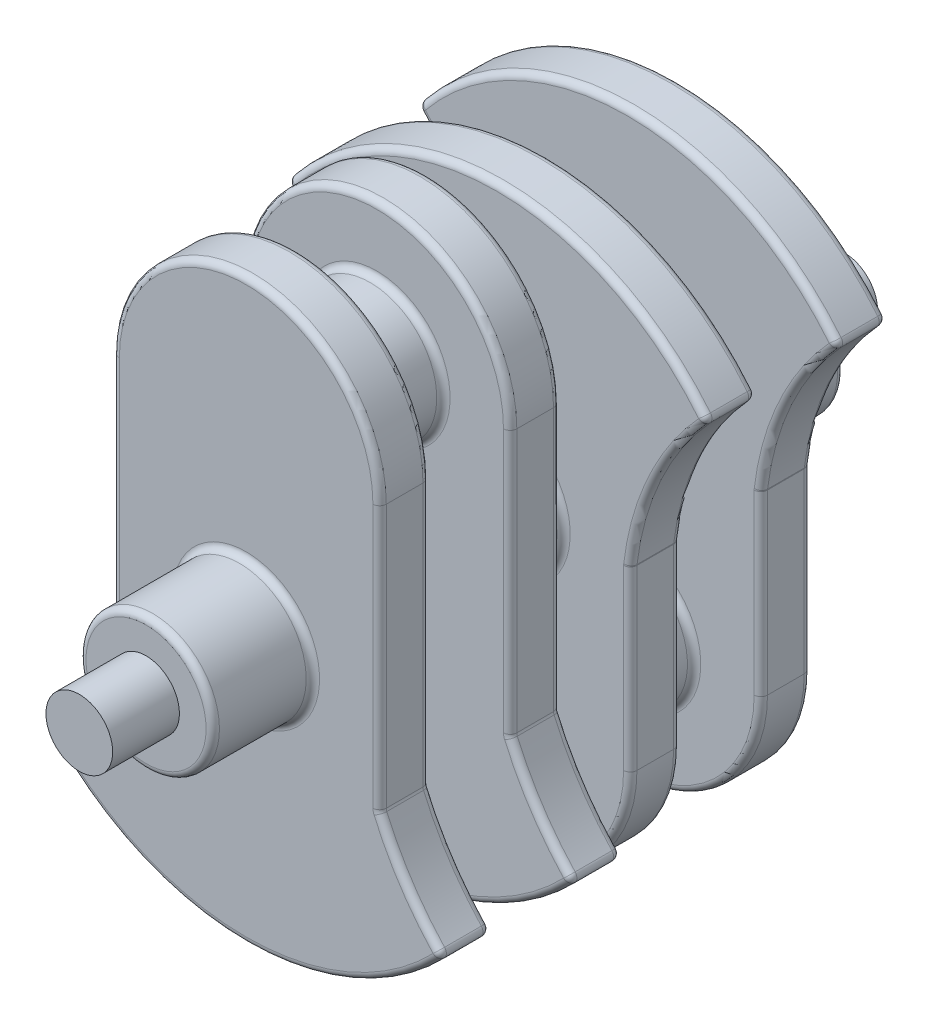
SolidWorks part; units mm, degrees
material "AISI 4340 Steel, normalized"
ref_plane "Front Plane" through (0, 0, 0) normal (0, 0, 1) x (1, 0, 0)
ref_plane "Top Plane" through (0, 0, 0) normal (0, 1, 0) x (1, 0, 0)
ref_plane "Right Plane" through (0, 0, 0) normal (1, 0, 0) x (0, 0, -1)
sketch "Sketch1" plane through (0, 0, 0) normal (0, 0, 1) x (1, 0, 0)
  circle A0 centre (0, 0) radius 20
  dimension "D1" = 20
extrude "Boss-Extrude1" add sketch "Sketch1" along normal blind 30
sketch "Sketch8" plane through (0, 0, 0) normal (0, 0, -1) x (-1, 0, 0)
  line L0 (-40, 53.333) -> (-40, -25.971)
  line L1 (40, 53.333) -> (40, -25.971)
  arc A0 (40, 53.333) -> (-40, 53.333) centre (0, 53.333) ccw
  arc A5 (-58.7669, -54.2813) -> (58.7669, -54.2813) centre (0, 0) ccw
  arc A6 (-40, -25.971) -> (-58.7669, -54.2813) centre (-125, 10) cw
  arc A7 (40, -25.971) -> (58.7669, -54.2813) centre (125, 10) ccw
  dimension "D1" = 40
  dimension "D2" = 80
  dimension "D3" = 53.333
  dimension "D5" = 10
  dimension "D6" = 125
extrude "Boss-Extrude5" add sketch "Sketch8" along normal blind 15
sketch "Sketch2" plane through (0, 0, 30) normal (0, 0, 1) x (1, 0, 0)
  circle A0 centre (0, 0) radius 10
  dimension "D1" = 10
extrude "Boss-Extrude2" add sketch "Sketch2" along normal blind 20
sketch "Sketch9" plane through (0, 0, -15) normal (0, 0, -1) x (-1, 0, 0)
  circle A0 centre (0, 53.333) radius 20
  dimension "D2" = 20
  dimension "D1" = 53.333
extrude "Boss-Extrude6" add sketch "Sketch9" along normal blind 24.13
ref_plane "Plane4" through (0, 0, -75.13) normal (0, 0, -1) x (-1, 0, 0)
sketch "Sketch10" plane through (0, 0, -39.13) normal (0, 0, -1) x (-1, 0, 0)
  line L0 (-40, -53.333) -> (-40, 0)
  line L1 (40, -53.333) -> (40, 0)
  arc A0 (-40, -53.333) -> (40, -53.333) centre (0, -53.333) ccw
  arc A1 (-40, 0) -> (-63.131, 49.1373) centre (-125, -10) ccw
  arc A2 (40, 0) -> (63.131, 49.1373) centre (125, -10) cw
  arc A3 (-63.131, 49.1373) -> (63.131, 49.1373) centre (0, 0) cw
  dimension "D1" = 40
  dimension "D5" = 10
  dimension "D3" = 80
  dimension "D2" = 53.333
  dimension "D4" = 125
extrude "Boss-Extrude7" add sketch "Sketch10" along normal blind 15 from surface starting at plane "Plane4"
ref_plane "Plane3" through (0, 0, -114.26) normal (0, 0, -1) x (-1, 0, 0)
sketch "Sketch12" plane through (0, 0, -114.26) normal (0, 0, -1) x (-1, 0, 0)
  line L2 (40, -53.333) -> (40, 0)
  line L3 (40, -53.333) -> (40, 0)
  line L4 (-40, 0) -> (-40, -53.333)
  line L5 (-40, 0) -> (-40, -53.333)
  arc A12 (-40, -53.333) -> (40, -53.333) centre (0, -53.333) ccw
  arc A13 (63.131, 49.1373) -> (40, 0) centre (125, -10) ccw
  arc A14 (63.131, 49.1373) -> (-63.131, 49.1373) centre (0, 0) ccw
  arc A15 (-40, 0) -> (-63.131, 49.1373) centre (-125, -10) ccw
  arc A16 (-40, -53.333) -> (40, -53.333) centre (0, -53.333) ccw
  arc A17 (63.131, 49.1373) -> (40, 0) centre (125, -10) ccw
  arc A18 (63.131, 49.1373) -> (-63.131, 49.1373) centre (0, 0) ccw
  arc A19 (-40, 0) -> (-63.131, 49.1373) centre (-125, -10) ccw
  dimension "D1" = 0
extrude "Boss-Extrude8" add sketch "Sketch12" along normal blind 15
sketch "Sketch14" plane through (0, 0, -90.13) normal (0, 0, -1) x (-1, 0, 0)
  circle A0 centre (0, -53.333) radius 20
  dimension "D2" = 20
  dimension "D1" = 53.333
extrude "Boss-Extrude9" add sketch "Sketch14" along normal up to next
sketch "Sketch15" plane through (0, 0, -129.26) normal (0, 0, -1) x (-1, 0, 0)
  circle A1 centre (0, 0) radius 20
  circle A2 centre (0, 0) radius 20
  dimension "D1" = 0
extrude "Boss-Extrude10" add sketch "Sketch15" along normal blind 30
sketch "Sketch16" plane through (0, 0, -159.26) normal (0, 0, -1) x (-1, 0, 0)
  circle A1 centre (0, 0) radius 10
  circle A2 centre (0, 0) radius 10
  dimension "D1" = 0
extrude "Boss-Extrude11" add sketch "Sketch16" along normal blind 20
sketch "Sketch18" plane through (0, 0, -39.13) normal (0, 0, -1) x (-1, 0, 0)
  line L2 (-40, 53.333) -> (-40, -25.971)
  line L3 (-40, 53.333) -> (-40, -25.971)
  line L4 (40, -25.971) -> (40, 53.333)
  line L5 (40, -25.971) -> (40, 53.333)
  arc A4 (40, 53.333) -> (-40, 53.333) centre (0, 53.333) ccw
  arc A5 (-58.7669, -54.2813) -> (-40, -25.971) centre (-125, 10) ccw
  arc A6 (-58.7669, -54.2813) -> (58.7669, -54.2813) centre (0, 0) ccw
  arc A7 (40, -25.971) -> (58.7669, -54.2813) centre (125, 10) ccw
  arc A8 (40, 53.333) -> (-40, 53.333) centre (0, 53.333) ccw
  arc A9 (-58.7669, -54.2813) -> (-40, -25.971) centre (-125, 10) ccw
  arc A10 (-58.7669, -54.2813) -> (58.7669, -54.2813) centre (0, 0) ccw
  arc A11 (40, -25.971) -> (58.7669, -54.2813) centre (125, 10) ccw
  dimension "D1" = 0
extrude "Boss-Extrude12" add sketch "Sketch18" along normal blind 15
sketch "Sketch19" plane through (0, 0, -54.13) normal (0, 0, -1) x (-1, 0, 0)
  circle A1 centre (0, 0) radius 20
  circle A2 centre (0, 0) radius 20
  dimension "D1" = 0
extrude "Boss-Extrude13" add sketch "Sketch19" along normal up to next
fillet "Fillet1" radius 2 32 edges at (0, -80, -39.13) (-48.0699, -40.9968, -39.13) (-40, 13.681, -39.13) (40, 13.681, -39.13) (48.0699, -40.9968, -39.13) (0, -80, -54.13) (-48.0699, -40.9968, -54.13) (-40, 13.681, -54.13) (0, 93.333, -54.13) (40, 13.681, -54.13) (48.0699, -40.9968, -54.13) (58.7669, -54.2813, -46.63) (40, -25.971, -46.63) (-40, -25.971, -46.63) (-58.7669, -54.2813, -46.63) (0, 93.333, -39.13) (40, 13.681, 0) (48.0699, -40.9968, 0) (0, -80, 0) (-48.0699, -40.9968, 0) (-40, 13.681, 0) (0, 93.333, -15) (40, 13.681, -15) (48.0699, -40.9968, -15) (0, -80, -15) (-48.0699, -40.9968, -15) (-40, 13.681, -15) (-40, -25.971, -7.5) (-58.7669, -54.2813, -7.5) (58.7669, -54.2813, -7.5) (40, -25.971, -7.5) (0, 93.333, 0)
fillet "Fillet2" radius 2 16 edges at (0, 80, -114.26) (47.5646, 26.4521, -114.26) (40, -26.6665, -114.26) (0, -93.333, -114.26) (-40, -26.6665, -114.26) (-47.5646, 26.4521, -114.26) (47.5646, 26.4521, -129.26) (40, -26.6665, -129.26) (0, -93.333, -129.26) (-40, -26.6665, -129.26) (-47.5646, 26.4521, -129.26) (-63.131, 49.1373, -121.76) (-40, 0, -121.76) (40, 0, -121.76) (63.131, 49.1373, -121.76) (0, 80, -129.26)
fillet "Fillet3" radius 2 16 edges at (40, -26.6665, -75.13) (47.5646, 26.4521, -75.13) (0, 80, -75.13) (-47.5646, 26.4521, -75.13) (-40, -26.6665, -75.13) (0, -93.333, -75.13) (40, -26.6665, -90.13) (47.5646, 26.4521, -90.13) (-47.5646, 26.4521, -90.13) (-40, -26.6665, -90.13) (0, -93.333, -90.13) (40, 0, -82.63) (63.131, 49.1373, -82.63) (-63.131, 49.1373, -82.63) (-40, 0, -82.63) (0, 80, -90.13)
fillet "Fillet5" radius 2 2 edges at (20, 0, 30) (20, 0, 0)
fillet "Fillet6" radius 2 2 edges at (-20, 0, -129.26) (-20, 0, -159.26)
ref_plane "Plane5" through (0, 20, 0) normal (0, 1, 0) x (1, 0, 0)
sketch "Sketch20" plane through (0, 0, 0) normal (1, 0, 0) x (0, 0, -1)
  line L1 (90.13, -73.333) -> (90.13, -33.333)
  line L2 (90.13, -73.333) -> (90.13, -33.333)
  dimension "D1" = 0
ref_plane "Plane6" through (0, -73.333, 0) normal (0, 1, 0) x (1, 0, 0)
sketch "Sketch21" plane through (0, 20, 0) normal (0, 1, 0) x (1, 0, 0)
  line L2 (-20, 157.26) -> (20, 157.26) construction
  line L3 (-20, 157.26) -> (-20, 131.26) construction
  line L4 (-20, 131.26) -> (20, 131.26) construction
  line L5 (20, 157.26) -> (20, 131.26) construction
  circle A0 centre (0, 144.26) radius 2.5
  point P10 (0, 157.26)
  point P11 (20, 144.26)
  dimension "D1" = 5
sketch "Sketch27" plane through (0, 0, 0) normal (0, 0, 1) x (1, 0, 0)
  line L0 (0, 73.333) -> (0, -20) construction
  circle A1 centre (0, 53.333) radius 20
  circle A2 centre (0, 53.333) radius 20 construction
  circle A3 centre (0, 0) radius 20
  circle A4 centre (0, 0) radius 20 construction
  dimension "D1" = 0
  dimension "D2" = 0
ref_plane "Plane8" through (0, 73.333, 0) normal (0, -1, 0) x (-1, 0, 0)
ref_plane "Plane9" through (0, -20, 0) normal (0, -1, 0) x (-1, 0, 0)
sketch "Sketch28" plane through (0, -20, 0) normal (0, -1, 0) x (-1, 0, 0)
  line L1 (-20, -2) -> (20, -2) construction
  line L2 (-20, -2) -> (-20, -28) construction
  line L3 (-20, -28) -> (20, -28) construction
  line L4 (20, -2) -> (20, -28) construction
  line L5 (-20, -2) -> (20, -28) construction
  line L6 (-20, -28) -> (20, -2) construction
  circle A0 centre (0, -15) radius 2.5
  point P4 (0, -15)
  dimension "D1" = 5
sketch "Sketch29" plane through (0, 73.333, 0) normal (0, -1, 0) x (-1, 0, 0)
  line L1 (20, 39.13) -> (-20, 39.13) construction
  line L2 (20, 39.13) -> (20, 15) construction
  line L3 (20, 15) -> (-20, 15) construction
  line L4 (-20, 39.13) -> (-20, 15) construction
  line L5 (20, 39.13) -> (-20, 15) construction
  line L6 (20, 15) -> (-20, 39.13) construction
  circle A0 centre (0, 27.065) radius 2.5
  point P4 (0, 27.065)
  dimension "D1" = 5
sketch "Sketch31" plane through (0, 0, 0) normal (1, 0, 0) x (0, 0, -1)
  line L0 (27.065, 73.333) -> (-15, -20) construction
ref_plane "Plane10" through (0, 73.333, -27.065) normal (0, -0.9117, 0.4109) x (-1, 0, 0)
hole_wizard "#26 (0.147) Diameter Hole2" positions "Sketch34" profile "Sketch35" hole size "#26" standard "ANSI Inch" end condition through all
sketch "Sketch34" plane through (0, 73.333, -27.065) normal (0, -0.9117, 0.4109) x (-1, 0, 0)
  point P0 (0, 0)
sketch "Sketch35" plane through (0, 73.333, -27.065) normal (1, 0, 0) x (0, -0.4109, -0.9117)
  line L0 (0, 0) -> (0, 68.6142)
  line L1 (0, 68.6142) -> (1.8669, 68.6142)
  line L2 (1.8669, 68.6142) -> (1.8669, 0.635)
  line L3 (1.8669, 0.635) -> (2.5019, 0)
  line L5 (2.5019, 0) -> (0, 0)
  line L6 (-1.8669, 0.635) -> (-2.5019, 0) construction
  line L11 (0, -6.35) -> (0, 107.95) construction
  dimension "Thru Hole Dia." = 3.7338
  dimension "Thru Hole Depth" = 68.6142
  dimension "Near C'Sink Dia." = 5.0038
  dimension "Near C'Sink Angle" = 90
ref_plane "Plane11" through (0, -20, 15) normal (0, -0.9117, 0.4109) x (-1, 0, 0)
hole_wizard "#26 (0.147) Diameter Hole1" positions "Sketch37" profile "Sketch38" hole size "#26" standard "ANSI Inch" end condition through all
sketch "Sketch37" plane through (0, -20, 15) normal (0, -0.9117, 0.4109) x (-1, 0, 0)
  point P0 (0, 0)
sketch "Sketch38" plane through (0, -20, 15) normal (1, 0, 0) x (0, -0.4109, -0.9117)
  line L0 (0, 0) -> (0, 170.9886)
  line L1 (0, 170.9886) -> (1.8669, 170.9886)
  line L2 (1.8669, 170.9886) -> (1.8669, 0.635)
  line L3 (1.8669, 0.635) -> (2.5019, 0)
  line L5 (2.5019, 0) -> (0, 0)
  line L6 (-1.8669, 0.635) -> (-2.5019, 0) construction
  line L11 (0, -6.35) -> (0, 107.95) construction
  dimension "Thru Hole Dia." = 3.7338
  dimension "Thru Hole Depth" = 170.9886
  dimension "Near C'Sink Dia." = 5.0038
  dimension "Near C'Sink Angle" = 90
combine bodies "Combine1" operation type add bodies to combine 123 109 117
fillet "Fillet7" radius 2 6 edges at (-20, 53.333, -39.13) (-20, 53.333, -15) (-20, 0, -54.13) (-20, 0, -75.13) (-20, -53.333, -114.26) (-20, -53.333, -90.13)
sketch "Sketch39" plane through (0, -73.333, 0) normal (0, 1, 0) x (1, 0, 0)
  line L1 (20, 112.26) -> (-20, 112.26) construction
  line L2 (20, 112.26) -> (20, 92.13) construction
  line L3 (20, 92.13) -> (-20, 92.13) construction
  line L4 (-20, 112.26) -> (-20, 92.13) construction
  line L5 (20, 112.26) -> (-20, 92.13) construction
  line L6 (20, 92.13) -> (-20, 112.26) construction
  point P4 (0, 102.195)
sketch "Sketch40" plane through (0, 0, 0) normal (1, 0, 0) x (0, 0, -1)
  line L0 (144.26, 20) -> (102.195, -73.333) construction
  line L1 (157.26, 20) -> (131.26, 20) construction
  point P5 (0, 0)
ref_plane "Plane12" through (0, 20, -144.26) normal (0, -0.9117, 0.4109) x (-1, 0, 0)
hole_wizard "#26 (0.147) Diameter Hole3" positions "Sketch42" profile "Sketch43" hole size "#26" standard "ANSI Inch" end condition through all
sketch "Sketch42" plane through (0, 20, -144.26) normal (0, -0.9117, 0.4109) x (-1, 0, 0)
  point P0 (0, 0)
sketch "Sketch43" plane through (0, 20, -144.26) normal (1, 0, 0) x (0, 0.4109, 0.9117)
  line L0 (0, 0) -> (0, 183.144)
  line L1 (0, 183.144) -> (1.8669, 183.144)
  line L2 (1.8669, 183.144) -> (1.8669, 0.635)
  line L3 (1.8669, 0.635) -> (2.5019, 0)
  line L5 (2.5019, 0) -> (0, 0)
  line L6 (-1.8669, 0.635) -> (-2.5019, 0) construction
  line L11 (0, -6.35) -> (0, 107.95) construction
  dimension "Thru Hole Dia." = 3.7338
  dimension "Thru Hole Depth" = 183.144
  dimension "Near C'Sink Dia." = 5.0038
  dimension "Near C'Sink Angle" = 90
ref_plane "Plane13" through (0, -73.333, -102.195) normal (0, -0.9117, 0.4109) x (-1, 0, 0)
hole_wizard "#26 (0.147) Diameter Hole4" positions "Sketch44" profile "Sketch45" hole size "#26" standard "ANSI Inch" end condition through all
sketch "Sketch44" plane through (0, -73.333, -102.195) normal (0, -0.9117, 0.4109) x (-1, 0, 0)
  point P0 (0, 0)
sketch "Sketch45" plane through (0, -73.333, -102.195) normal (1, 0, 0) x (0, -0.4109, -0.9117)
  line L0 (0, 0) -> (0, 183.6121)
  line L1 (0, 183.6121) -> (1.8669, 183.6121)
  line L2 (1.8669, 183.6121) -> (1.8669, 0.635)
  line L3 (1.8669, 0.635) -> (2.5019, 0)
  line L5 (2.5019, 0) -> (0, 0)
  line L6 (-1.8669, 0.635) -> (-2.5019, 0) construction
  line L11 (0, -6.35) -> (0, 107.95) construction
  dimension "Thru Hole Dia." = 3.7338
  dimension "Thru Hole Depth" = 183.6121
  dimension "Near C'Sink Dia." = 5.0038
  dimension "Near C'Sink Angle" = 90
equation "\"Crank Radius\"= 53.333mm"
equation "\"D1@Sketch9\"=\"Crank Radius\""
equation "\"D1@Sketch14\"=\"Crank Radius\""
equation "\"Journal Radius\"= 20mm"
equation "\"D1@Sketch1\"=\"Journal Radius\""
equation "\"D2@Sketch9\"=\"Journal Radius\""
equation "\"D2@Sketch14\"=\"Journal Radius\""
equation "\"Lobe Thickness\"= 15mm"
equation "\"D1@Boss-Extrude5\"=\"Lobe Thickness\""
equation "\"D1@Boss-Extrude7\"=\"Lobe Thickness\""
equation "\"D1@Boss-Extrude8\"=\"Lobe Thickness\""
equation "\"D1@Boss-Extrude12\"=\"Lobe Thickness\""
equation "\"D3@Sketch8\"=\"Crank Radius\""
equation "\"D2@Sketch10\"=\"Crank Radius\""
